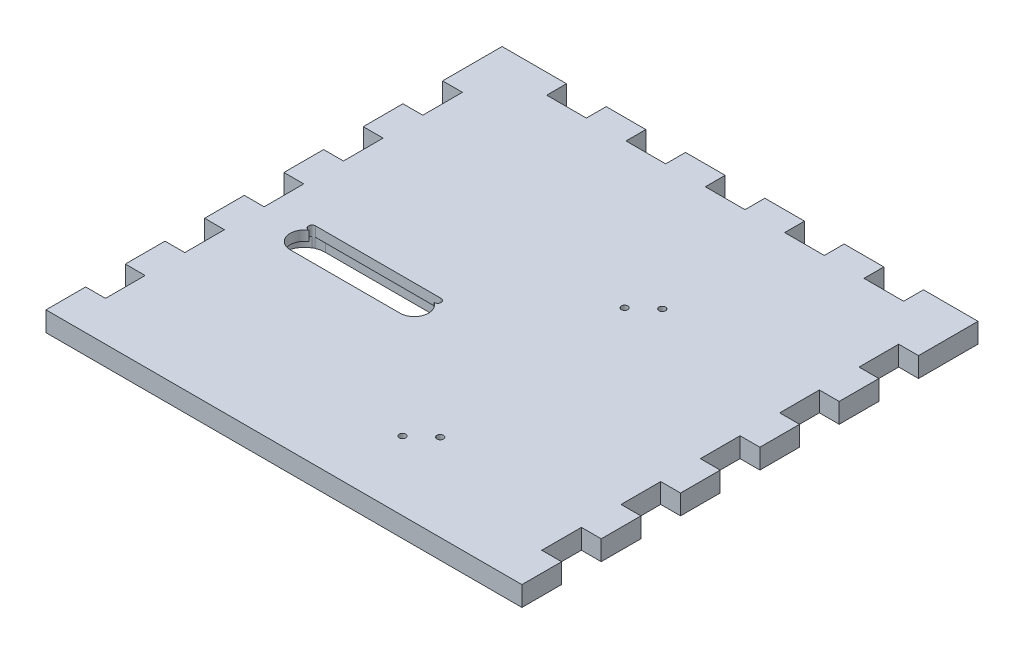
SolidWorks part; units mm, degrees
ref_plane "Front Plane" through (0, 0, 0) normal (0, 0, 1) x (1, 0, 0)
ref_plane "Top Plane" through (0, 0, 0) normal (0, 1, 0) x (1, 0, 0)
ref_plane "Right Plane" through (0, 0, 0) normal (1, 0, 0) x (0, 0, -1)
sketch "Sketch1" plane through (0, 0, 0) normal (0, 1, 0) x (1, 0, 0)
  line L1 (-139.7, -139.7) -> (139.7, -139.7)
  line L2 (-139.7, -139.7) -> (-139.7, 139.7)
  line L3 (-139.7, 139.7) -> (139.7, 139.7)
  line L4 (139.7, -139.7) -> (139.7, 139.7)
  line L5 (-139.7, -139.7) -> (139.7, 139.7) construction
  line L6 (-139.7, 139.7) -> (139.7, -139.7) construction
  point P0 (0, 0)
  dimension "D1" = 279.4
  dimension "D2" = 279.4
extrude "Boss-Extrude1" add sketch "Sketch1" along normal blind 12.7
sketch "Sketch2" plane through (139.7, 0, 0) normal (1, 0, 0) x (0, 0, -1)
  line L0 (-139.7, 12.7) -> (139.7, 12.7) construction
  line L1 (-139.7, 0) -> (-114.3, 0)
  line L2 (-139.7, 0) -> (-139.7, 12.7)
  line L3 (-139.7, 12.7) -> (-114.3, 12.7)
  line L4 (-114.3, 0) -> (-114.3, 12.7)
  dimension "D1" = 25.4
extrude "Boss-Extrude2" add sketch "Sketch2" along normal blind 12.7
pattern_linear "LPattern1" count 6 spacing 50.8 along (0, 0, -1) of "Boss-Extrude2"
mirror "Mirror1" about plane through (0, 0, 0) normal (1, 0, 0) of "LPattern1"
sketch "Sketch3" plane through (0, 0, -139.7) normal (0, 0, -1) x (-1, 0, 0)
  line L0 (-152.4, 12.7) -> (152.4, 12.7) construction
  line L1 (-142.875, 12.7) -> (-117.475, 12.7)
  line L2 (-142.875, 12.7) -> (-142.875, 0)
  line L3 (-142.875, 0) -> (-117.475, 0)
  line L4 (-117.475, 12.7) -> (-117.475, 0)
  line L5 (-152.4, 0) -> (152.4, 0) construction
  line L6 (-152.4, 0) -> (-152.4, 12.7) construction
  dimension "D1" = 9.525
  dimension "D2" = 25.4
extrude "Boss-Extrude3" add sketch "Sketch3" along normal blind 12.7
pattern_linear "LPattern2" count 6 spacing 50.8 along (-1, 0, 0) of "Boss-Extrude3"
sketch "Sketch5" plane through (0, 0, -139.7) normal (0, 0, -1) x (-1, 0, 0)
  line L11 (160.655, 0) -> (-160.655, 0) construction
  line L12 (-152.4, 12.7) -> (-127, 12.7)
  line L13 (-152.4, 12.7) -> (-152.4, 0)
  line L14 (-152.4, 0) -> (-127, 0)
  line L15 (-127, 12.7) -> (-127, 0)
  dimension "D1" = 25.4
extrude "Boss-Extrude4" add sketch "Sketch5" along normal blind 12.7
mirror "Mirror2" about plane through (0, 0, 0) normal (1, 0, 0) of "Boss-Extrude4"
sketch "Sketch6" plane through (0, 0, 0) normal (0, -1, 0) x (1, 0, 0)
  circle A0 centre (44.45, -58.1456) radius 2.1 construction
  circle A1 centre (44.45, -58.1456) radius 2.1
  circle A2 centre (31.75, -46.7156) radius 2.1 construction
  circle A3 centre (31.75, -46.7156) radius 2.1
  circle A4 centre (31.75, 95.5244) radius 2.1 construction
  circle A5 centre (31.75, 95.5244) radius 2.1
  circle A6 centre (44.45, 84.0944) radius 2.1 construction
  circle A7 centre (44.45, 84.0944) radius 2.1
extrude "Cut-Extrude1" cut sketch "Sketch6" against normal through all
sketch "Sketch7" plane through (0, 0, 0) normal (0, -1, 0) x (1, 0, 0)
  circle A0 centre (31.75, 95.5244) radius 4.318
  circle A1 centre (31.75, 95.5244) radius 2.1 construction
  circle A2 centre (44.45, 84.0944) radius 4.318
  circle A3 centre (31.75, -46.7156) radius 4.318
  circle A4 centre (44.45, -58.1456) radius 4.318
  dimension "D1" = 8.636
  dimension "D2" = 8.636
  dimension "D3" = 8.636
  dimension "D4" = 8.636
extrude "Cut-Extrude2" cut sketch "Sketch7" against normal blind 6.35
sketch "Sketch8" plane through (0, 12.7, 0) normal (0, 1, 0) x (1, 0, 0)
  circle A0 centre (-49.9203, -19.0839) radius 2.2225 construction
  circle A1 centre (-49.9203, -19.0839) radius 2.2225
  circle A2 centre (-44.9203, -9.0839) radius 2.2225 construction
  circle A3 centre (-44.9203, -9.0839) radius 2.2225
  circle A4 centre (-94.9203, -19.0839) radius 2.2225 construction
  circle A5 centre (-94.9203, -19.0839) radius 2.2225
  circle A6 centre (-99.9203, -9.0839) radius 2.2225 construction
  circle A7 centre (-99.9203, -9.0839) radius 2.2225
extrude "Cut-Extrude3" cut sketch "Sketch8" against normal through all
sketch "Sketch9" plane through (0, 0, 0) normal (0, -1, 0) x (1, 0, 0)
  circle A0 centre (-94.9203, 19.0839) radius 6.35
  circle A1 centre (-99.9203, 9.0839) radius 6.35
  circle A2 centre (-44.9203, 9.0839) radius 6.35
  circle A3 centre (-49.9203, 19.0839) radius 6.35
  dimension "D1" = 12.7
  dimension "D2" = 12.7
  dimension "D3" = 12.7
  dimension "D4" = 12.7
extrude "Cut-Extrude4" cut sketch "Sketch9" against normal blind 6.35 rebuild error yes
sketch "Sketch10" plane through (0, 0, 0) normal (0, -1, 0) x (1, 0, 0)
  line L0 (-94.9203, 19.0839) -> (-49.9203, 19.0839) construction
  line L1 (-49.9203, 19.0839) -> (-37.1427, 19.0839) construction
  line L2 (-94.9203, 19.0839) -> (-107.5477, 19.0839) construction
  line L3 (-44.9203, 9.0839) -> (-99.9203, 9.0839) construction
  line L4 (-99.9203, 9.0839) -> (-112.6283, 9.0839) construction
  line L5 (-44.9203, 9.0839) -> (-32.1847, 9.0839) construction
  line L6 (-107.5477, 19.0839) -> (-37.1427, 19.0839) construction
  line L7 (-107.5477, 32.3162) -> (-37.1427, 32.3162)
  line L8 (-107.5477, 5.8516) -> (-37.1427, 5.8516)
  line L9 (-112.6283, 9.0839) -> (-32.1847, 9.0839) construction
  line L10 (-112.6283, 12.1304) -> (-32.1847, 12.1304)
  line L11 (-112.6283, 6.0374) -> (-32.1847, 6.0374)
  line L12 (-112.6283, 9.0839) -> (-32.1847, 9.0839) construction
  line L13 (-112.6283, 11.3489) -> (-32.1847, 11.3489)
  line L14 (-112.6283, 6.8189) -> (-32.1847, 6.8189)
  line L15 (-107.5477, 19.0839) -> (-37.1427, 19.0839) construction
  line L16 (-107.5477, 28.2001) -> (-37.1427, 28.2001)
  line L17 (-107.5477, 9.9677) -> (-37.1427, 9.9677)
  arc A0 (-107.5477, 32.3162) -> (-107.5477, 5.8516) centre (-107.5477, 19.0839) ccw
  arc A1 (-37.1427, 5.8516) -> (-37.1427, 32.3162) centre (-37.1427, 19.0839) ccw
  arc A2 (-112.6283, 12.1304) -> (-112.6283, 6.0374) centre (-112.6283, 9.0839) ccw
  arc A3 (-32.1847, 6.0374) -> (-32.1847, 12.1304) centre (-32.1847, 9.0839) ccw
  arc A4 (-112.6283, 11.3489) -> (-112.6283, 6.8189) centre (-112.6283, 9.0839) ccw
  arc A5 (-32.1847, 6.8189) -> (-32.1847, 11.3489) centre (-32.1847, 9.0839) ccw
  arc A6 (-107.5477, 28.2001) -> (-107.5477, 9.9677) centre (-107.5477, 19.0839) ccw
  arc A7 (-37.1427, 9.9677) -> (-37.1427, 28.2001) centre (-37.1427, 19.0839) ccw
  point P4 (-72.3452, 19.0839)
  point P17 (-72.4065, 9.0839)
  point P22 (-72.4065, 9.0839)
  point P29 (-72.3452, 19.0839)
extrude "Cut-Extrude5" cut sketch "Sketch10" against normal through all contours L16 A7 L17 A6 | L14 A5 L13 A4
sketch "Sketch12" plane through (0, 0, 0) normal (0, -1, 0) x (1, 0, 0)
  line L0 (-107.5477, 19.0839) -> (-37.7917, 19.0839) construction
  line L1 (-107.5477, 32.4644) -> (-37.7917, 32.4644)
  line L2 (-107.5477, 5.7034) -> (-37.7917, 5.7034)
  arc A0 (-107.5477, 32.4644) -> (-107.5477, 5.7034) centre (-107.5477, 19.0839) ccw
  arc A1 (-37.7917, 5.7034) -> (-37.7917, 32.4644) centre (-37.7917, 19.0839) ccw
  point P3 (-72.6697, 19.0839)
extrude "Cut-Extrude6" cut sketch "Sketch12" against normal blind 6.35
extrude "Cut-Extrude7" cut sketch "Sketch10<3>" against normal blind 6.35 rebuild error yes
sketch "Sketch10<3>" plane through (0, 0, 0) normal (0, -1, 0) x (1, 0, 0) same geometry as "Sketch10"
